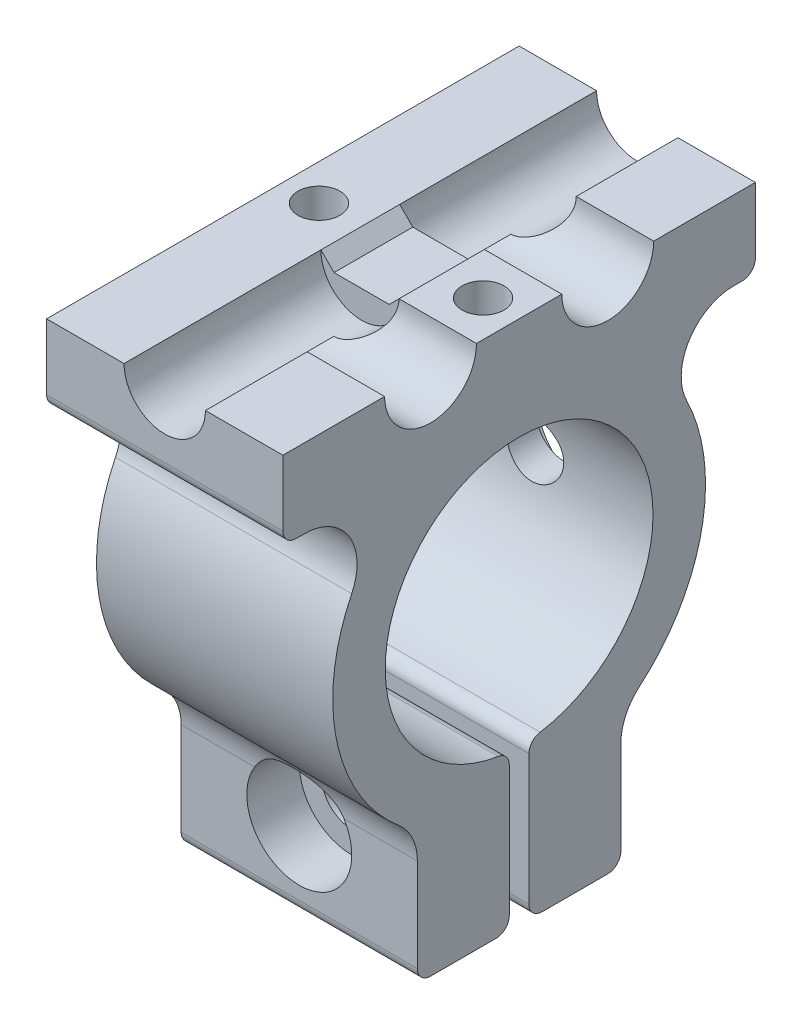
SolidWorks part; units mm, degrees
ref_plane "Спереди" through (0, 0, 0) normal (0, 0, 1) x (1, 0, 0)
ref_plane "Сверху" through (0, 0, 0) normal (0, 1, 0) x (1, 0, 0)
ref_plane "Справа" through (0, 0, 0) normal (1, 0, 0) x (0, 0, -1)
other "Configuration Table"
sketch "Эскиз1" plane through (0, 0, 0) normal (1, 0, 0) x (0, 0, -1)
  line L0 (-1001.0275, 18) -> (48998.9725, 18) construction
  line L1 (0, -1000) -> (0, 49000) construction
  line L2 (-0.75, -21) -> (-0.75, -11.0624)
  line L3 (0.75, -21) -> (0.75, -11.0624)
  line L4 (7.75, -13.8988) -> (7.75, -21)
  line L5 (-7.75, -13.8988) -> (-7.75, -21)
  line L6 (1.75, -22) -> (6.75, -22)
  line L7 (-1000, 0) -> (49000, 0) construction
  line L8 (-6.75, -22) -> (-1.75, -22)
  line L9 (-18, 18) -> (-18, 13)
  line L10 (-7.75, -6.6316) -> (-7.75, -11.8986) construction
  line L11 (7.75, -6.6316) -> (7.75, -11.8986) construction
  line L12 (-17, 12) -> (-16.3475, 12)
  line L13 (17, 12) -> (16.3475, 12)
  line L14 (18, 18) -> (18, 13)
  line L15 (-18, 18) -> (18, 18)
  arc A0 (1.5938, -10.0747) -> (-1.5938, -10.0747) centre (0, 0) ccw
  arc A1 (9.1676, -10.8441) -> (12.7546, 6.2418) centre (0, 0) ccw
  arc A2 (0, -10.2) -> (0.75, -10.1724) centre (0, 0) ccw construction
  arc A3 (-0.75, -10.1724) -> (0, -10.2) centre (0, 0) ccw construction
  arc A4 (0, -14.2) -> (0.75, -14.1802) centre (0, 0) ccw construction
  arc A5 (-0.75, -14.1802) -> (0, -14.2) centre (0, 0) ccw construction
  arc A6 (-7.75, -11.8986) -> (-0.75, -14.1802) centre (0, 0) ccw construction
  arc A7 (0.75, -14.1802) -> (7.75, -11.8986) centre (0, 0) ccw construction
  arc A8 (0, 14.2) -> (-7.5921, 12) centre (0, 0) ccw construction
  arc A9 (-12.7546, 6.2418) -> (-9.1676, -10.8441) centre (0, 0) ccw
  arc A10 (7.5921, 12) -> (0, 14.2) centre (0, 0) ccw construction
  arc A11 (16.3475, 12) -> (12.7546, 6.2418) centre (16.3475, 8) ccw
  arc A12 (-16.3475, 12) -> (-12.7546, 6.2418) centre (-16.3475, 8) cw
  arc A13 (9.1676, -10.8441) -> (7.75, -13.8988) centre (11.75, -13.8988) ccw
  arc A14 (-9.1676, -10.8441) -> (-7.75, -13.8988) centre (-11.75, -13.8988) cw
  arc A15 (18, 13) -> (17, 12) centre (17, 13) cw
  arc A16 (-18, 13) -> (-17, 12) centre (-17, 13) ccw
  arc A17 (1.5938, -10.0747) -> (0.75, -11.0624) centre (1.75, -11.0624) ccw
  arc A18 (-0.75, -11.0624) -> (-1.5938, -10.0747) centre (-1.75, -11.0624) ccw
  arc A19 (7.75, -21) -> (6.75, -22) centre (6.75, -21) cw
  arc A20 (-7.75, -21) -> (-6.75, -22) centre (-6.75, -21) ccw
  arc A21 (1.75, -22) -> (0.75, -21) centre (1.75, -21) cw
  arc A22 (-0.75, -21) -> (-1.75, -22) centre (-1.75, -21) cw
  point P43 (18, 12)
  point P46 (-18, 12)
  point P55 (7.75, -22)
  point P58 (-7.75, -22)
  point P63 (-0.75, -22)
  dimension "D1" = 20.4
  dimension "D2" = 4
  dimension "D9" = 4
  dimension "D10" = 4
  dimension "D11" = 4
  dimension "D12" = 4
  dimension "D13" = 1
  dimension "D14" = 1
  dimension "D15" = 1
  dimension "D16" = 1
  dimension "D17" = 1
  dimension "D18" = 1
  dimension "D19" = 1
  dimension "D20" = 1
  dimension "D3" = 18
  dimension "D4" = 1.5
  dimension "D5" = 15.5
  dimension "D6" = 36
  dimension "D7" = 6
  dimension "D8" = 22
extrude "Бобышка-Вытянуть1" add sketch "Эскиз1" along normal mid plane 18
sketch "Эскиз2" plane through (0, 0, 0) normal (0, 0, 1) x (1, 0, 0)
  line L0 (9, -22) -> (-9, -22) construction
  line L1 (9, -22) -> (-9, -22)
  line L2 (0, -1000) -> (0, 49000) construction
  line L3 (9, 18) -> (-9, 18) construction
  line L4 (9, 18) -> (-9, 18)
  circle A0 centre (0, -16) radius 2.3
  arc A1 (-3.1, 18) -> (3.1, 18) centre (0, 18) ccw
  arc A2 (3.1, 18) -> (0, 21.1) centre (0, 18) ccw construction
  arc A3 (0, 21.1) -> (-3.1, 18) centre (0, 18) ccw construction
  dimension "D2" = 4.6
  dimension "D3" = 6.2
  dimension "D1" = 6
extrude "Вырез-Вытянуть1" cut sketch "Эскиз2" against normal through all both and the other way through all contours L4 A1 | A0 region at (0, 16.6843, 0) region at (0, -16, 0)
sketch "Эскиз3" plane through (0, 0, -7.75) normal (0, 0, -1) x (-1, 0, 0)
  line L0 (0, -1016) -> (0, 48984) construction
  line L1 (-1000, -16) -> (49000, -16) construction
  line L3 (-4.6188, -16) -> (-2.3094, -20)
  line L4 (-2.3094, -20) -> (2.3094, -20)
  line L5 (9, -13.8988) -> (0.9355, -13.8988)
  line L6 (-0.9355, -13.8988) -> (-9, -13.8988)
  line L7 (-9, -13.8988) -> (-9, -21)
  line L8 (-9, -21) -> (9, -21)
  line L9 (9, -21) -> (9, -13.8988)
  line L10 (9, -13.8988) -> (0.9355, -13.8988)
  line L11 (-0.9355, -13.8988) -> (-9, -13.8988)
  line L12 (-9, -13.8988) -> (-9, -21)
  line L13 (-9, -21) -> (9, -21)
  line L14 (9, -21) -> (9, -13.8988)
  line L15 (2.3094, -20) -> (4.6188, -16)
  line L16 (4.6188, -16) -> (2.3094, -12)
  line L17 (2.3094, -12) -> (-2.3094, -12)
  line L18 (-2.3094, -12) -> (-4.6188, -16)
  circle A0 centre (0, -16) radius 4 construction
  arc A1 (-0.9355, -13.8988) -> (0.9355, -13.8988) centre (0, -16) ccw
  arc A2 (-0.9355, -13.8988) -> (0.9355, -13.8988) centre (0, -16) ccw
  arc M10 (0.9355, -13.8988) -> (-0.9355, -13.8988) centre (0, -16) cw
  line M11 (-0.9355, -13.8988) -> (-9, -13.8988)
  dimension "D2" = 8
  dimension "D1" = 0
extrude "Вырез-Вытянуть2" cut sketch "Эскиз3" against normal blind 3.3 and the other way through all draft 1 contours L18 L3 L4 L15 L16 L10 M11 M10 | L17 L18 L10 L16 M11 M10 region at (3.9164, -15.0048, -7.75) region at (0, -14.8281, -7.75)
sketch "Эскиз4" plane through (0, 0, 7.75) normal (0, 0, 1) x (1, 0, 0)
  arc A0 (-0.9355, -13.8988) -> (0.9355, -13.8988) centre (0, -16) ccw construction
  arc A1 (-0.9355, -13.8988) -> (0.9355, -13.8988) centre (0, -16) ccw
  circle A2 centre (0, -16) radius 4
  line M1 (9, -13.8988) -> (0.9355, -13.8988)
  arc M2 (0.9355, -13.8988) -> (-0.9355, -13.8988) centre (0, -16) cw
  line M3 (-0.9355, -13.8988) -> (-9, -13.8988)
  dimension "D1" = 8
extrude "Вырез-Вытянуть3" cut sketch "Эскиз4" against normal blind 4 and the other way through all contours A2 M3 M1 M2 | A2 M1 M3 M2 region at (0, -14.9905, 7.75) region at (0, -18.4006, 7.75)
sketch "Эскиз5" plane through (0, 18, 0) normal (0, 1, 0) x (1, 0, 0)
  line L0 (-1000, 0) -> (49000, 0) construction
  line L1 (0, -1000) -> (0, 49000) construction
  circle A0 centre (6.25, 0) radius 1.6
  circle A1 centre (-6.25, 0) radius 1.6
  dimension "D1" = 3.2
  dimension "D2" = 12.5
extrude "Вырез-Вытянуть4" cut sketch "Эскиз5" against normal up to surface (7.9263 mm away) up to face at (0, 0.0626, 0)
sketch "Эскиз6" plane through (0, 0, 0) normal (0, 0, 1) x (1, 0, 0)
  line L0 (-3.1, 18) -> (3.1, 18)
  arc A0 (-3.1, 18) -> (3.1, 18) centre (0, 18) ccw construction
  arc A1 (-3.1, 18) -> (3.1, 18) centre (0, 18) ccw
extrude "Бобышка-Вытянуть2" add sketch "Эскиз6" along normal mid plane 6
sketch "Эскиз7" plane through (0, 18, 0) normal (0, 1, 0) x (1, 0, 0)
  line L0 (3.1, 3) -> (-3.1, 3) construction
  line L1 (3.1, 3) -> (3.1, 18) construction
  line L2 (3.1, 18) -> (-3.1, 18) construction
  line L3 (-3.1, 18) -> (-3.1, 3) construction
  line L4 (3.1, -18) -> (3.1, -3) construction
  line L5 (-3.1, -3) -> (3.1, -3) construction
  line L6 (-3.1, -3) -> (-3.1, -18) construction
  line L7 (-3.1, -18) -> (3.1, -18) construction
  line L8 (3.1, 3) -> (-3.1, 3)
  line L9 (3.1, 3) -> (3.1, 18)
  line L10 (3.1, 18) -> (-3.1, 18)
  line L11 (-3.1, 18) -> (-3.1, 3)
  line L12 (3.1, -18) -> (3.1, -3)
  line L13 (-3.1, -3) -> (3.1, -3)
  line L14 (-3.1, -3) -> (-3.1, -18)
  line L15 (-3.1, -18) -> (3.1, -18)
  line L16 (-3.1, 3) -> (-3.1, -3)
  line L17 (3.1, 3) -> (3.1, -3)
  line M8 (-3.1, -3) -> (3.1, -3)
  line M14 (3.1, 3) -> (-3.1, 3)
extrude "Вырез-Вытянуть6" cut sketch "Эскиз7" against normal blind 1 contours L17 L16 M14 M8 region at (0, 18, 0)
chamfer "Фаска3" distance 1 angle 45 2 edges at (3.1, 17, 0) (-3.1, 17, 0)
sketch "Эскиз8" plane through (9, 0, 0) normal (1, 0, 0) x (0, 0, -1)
  line L0 (18, 18) -> (-18, 18) construction
  line L1 (18, 18) -> (-18, 18)
  line L2 (0, -1000) -> (0, 49000) construction
  line L3 (-10.25, 18) -> (-3.25, 18)
  line L4 (3.25, 18) -> (10.25, 18)
  arc A0 (-10.25, 18) -> (-3.25, 18) centre (-6.75, 18) ccw
  arc A1 (10.25, 18) -> (3.25, 18) centre (6.75, 18) cw
  dimension "D1" = 3.5
  dimension "D2" = 13.5
extrude "Вырез-Вытянуть8" cut sketch "Эскиз8" against normal up to surface (5.9 mm away) contours L1 A0 | A1 L1 region at (9, 16.5146, -6.75) region at (9, 16.5146, 6.75) up to face at (2.6, 17.5, 0)
sketch "Эскиз9" plane through (0, 0, 0) normal (0, 0, 1) x (1, 0, 0)
  circle A0 centre (0, 0) radius 2.2
  dimension "D1" = 4.4
extrude "Вырез-Вытянуть9" cut sketch "Эскиз9" against normal through all
ref_plane "Плоскость1" through (0, 0, -18) normal (0, 0, 1) x (1, 0, 0)
sketch "Эскиз10" plane through (0, 0, -18) normal (0, 0, 1) x (1, 0, 0)
  circle A0 centre (0, 0) radius 2.2 construction
  circle A1 centre (0, 0) radius 2.2
  circle A2 centre (0, 0) radius 4
  dimension "D1" = 8
extrude "Вырез-Вытянуть10" cut sketch "Эскиз10" along normal blind 5.5
